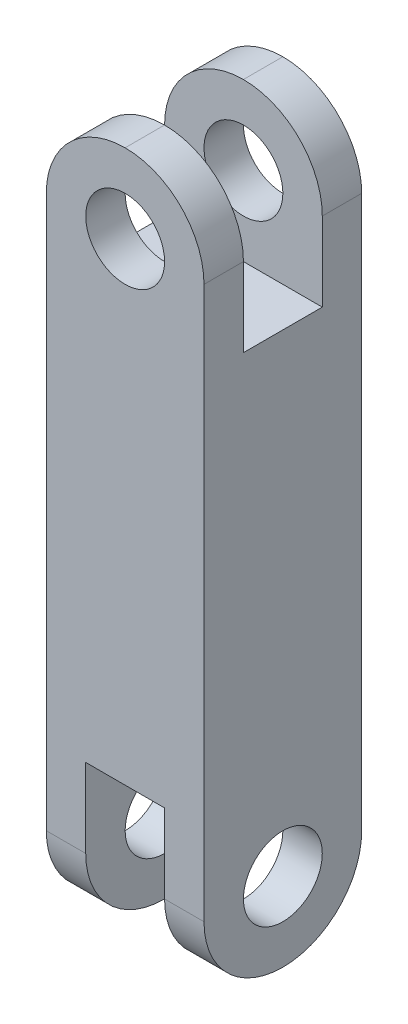
SolidWorks part; units mm, degrees
ref_plane "Front Plane" through (0, 0, 0) normal (0, 0, 1) x (1, 0, 0)
ref_plane "Top Plane" through (0, 0, 0) normal (0, 1, 0) x (1, 0, 0)
ref_plane "Right Plane" through (0, 0, 0) normal (1, 0, 0) x (0, 0, -1)
sketch "Sketch2" plane through (0, 0, 0) normal (0, 1, 0) x (1, 0, 0)
  line L1 (-50.8, -50.8) -> (50.8, -50.8)
  line L2 (-50.8, -50.8) -> (-50.8, 50.8)
  line L3 (-50.8, 50.8) -> (50.8, 50.8)
  line L4 (50.8, -50.8) -> (50.8, 50.8)
  line L5 (-50.8, -50.8) -> (50.8, 50.8) construction
  line L6 (-50.8, 50.8) -> (50.8, -50.8) construction
  point P0 (0, 0)
  dimension "D1" = 101.6
  dimension "D2" = 101.6
extrude "Boss-Extrude1" add sketch "Sketch2" along normal blind 457.2
sketch "Sketch3" plane through (0, 0, 0) normal (0, 0, 1) x (1, 0, 0)
  line L0 (-50.8, 0) -> (50.8, 0) construction
  line L1 (-25.4, 0) -> (25.4, 0)
  line L2 (-25.4, 0) -> (-25.4, 101.6)
  line L3 (-25.4, 101.6) -> (25.4, 101.6)
  line L4 (25.4, 0) -> (25.4, 101.6)
  line L5 (-50.8, 457.2) -> (-50.8, 0) construction
  line L6 (-50.8, 457.2) -> (50.8, 457.2) construction
  circle A0 centre (0, 406.4) radius 25.4
  dimension "D4" = 50.8
  dimension "D1" = 50.8
  dimension "D2" = 101.6
  dimension "D3" = 25.4
  dimension "D5" = 50.8
extrude "Cut-Extrude1" cut sketch "Sketch3" against normal through all both and the other way through all
fillet "Fillet1" radius 50.8 6 edges at (-38.1, 0, -50.8) (-38.1, 0, 50.8) (38.1, 0, -50.8) (38.1, 0, 50.8) (-50.8, 457.2, 0) (50.8, 457.2, 0)
sketch "Sketch4" plane through (50.8, 0, 0) normal (1, 0, 0) x (0, 0, -1)
  line L1 (-25.4, 355.6) -> (25.4, 355.6)
  line L2 (-25.4, 355.6) -> (-25.4, 457.2)
  line L3 (-25.4, 457.2) -> (25.4, 457.2)
  line L4 (25.4, 355.6) -> (25.4, 457.2)
  line L6 (-50.8, 457.2) -> (-50.8, 406.4) construction
  circle A0 centre (0, 50.8) radius 25.4
  dimension "D1" = 50.8
  dimension "D2" = 50.8
  dimension "D3" = 50.8
  dimension "D4" = 25.4
  dimension "D5" = 101.6
extrude "Cut-Extrude2" cut sketch "Sketch4" against normal through all both
